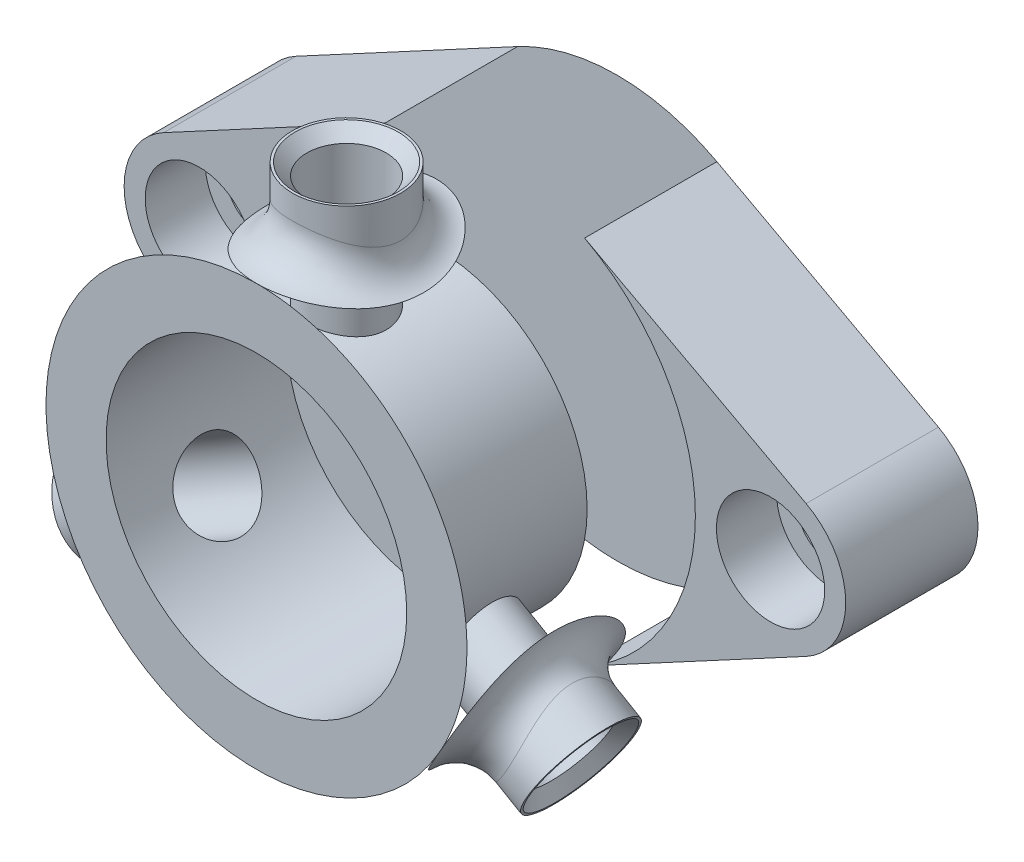
SolidWorks part; units mm, degrees
ref_plane "Front Plane" through (0, 0, 0) normal (0, 0, 1) x (1, 0, 0)
ref_plane "Top Plane" through (0, 0, 0) normal (0, 1, 0) x (1, 0, 0)
ref_plane "Right Plane" through (0, 0, 0) normal (1, 0, 0) x (0, 0, -1)
sketch "Sketch1" plane through (0, 0, 0) normal (0, 0, 1) x (1, 0, 0)
  circle A0 centre (0, 0) radius 12.5
  circle A1 centre (0, 0) radius 17.5
  dimension "D1" = 25
  dimension "D2" = 5
extrude "Boss-Extrude1" add sketch "Sketch1" along normal blind 15
sketch "Sketch2" plane through (0, 0, 0) normal (0, 0, -1) x (-1, 0, 0)
  circle A0 centre (0, 0) radius 17.5
  dimension "D1" = 35
extrude "Boss-Extrude2" add sketch "Sketch2" along normal blind 15
ref_plane "Plane1" through (0, 22.5, 0) normal (0, 1, 0) x (1, 0, 0)
sketch "Sketch3" plane through (0, 22.5, 0) normal (0, 1, 0) x (1, 0, 0)
  line L0 (-17.5, -15) -> (17.5, -15) construction
  circle A0 centre (0, -7.5) radius 4.5
  dimension "D1" = 9
  dimension "D2" = 7.5
extrude "Boss-Extrude3" add sketch "Sketch3" against normal up to surface (5 mm away) up to face at (17.5, 0, 15)
sketch "Sketch4" plane through (0, 22.5, 0) normal (0, 1, 0) x (1, 0, 0)
  circle A0 centre (0, -7.5) radius 3.3
  dimension "D1" = 6.6
extrude "Cut-Extrude1" cut sketch "Sketch4" against normal up to surface (10 mm away) up to face at (12.5, 0, 15)
pattern_circular "CirPattern1" count 3 over 360 about axis through (0, 0, 15) along (0, 0, 1) of "Boss-Extrude3", "Cut-Extrude1"
fillet "Fillet1" radius 3 3 edges at (12.458, -12.2901, 6.6272) (-16.8726, -4.6439, 6.6272) (-0.8714, 17.4783, 3.0852)
chamfer "Chamfer1" distance 1 angle 45 3 edges at (-19.4856, -11.25, 10.8) (19.4856, -11.25, 10.8) (0, 22.5, 10.8)
sketch "Sketch5" plane through (0, 0, -15) normal (0, 0, -1) x (-1, 0, 0)
  line L0 (26.7105, 5.5043) -> (8.2895, 15.4122)
  line L1 (26.7105, -5.5043) -> (8.2895, -15.4122)
  line L2 (-8.2895, 15.4122) -> (-26.7105, 5.5043)
  line L3 (-8.2895, -15.4122) -> (-26.7105, -5.5043)
  circle A0 centre (23.75, 0) radius 2.75
  circle A1 centre (-23.75, 0) radius 2.75
  arc A2 (26.7105, -5.5043) -> (26.7105, 5.5043) centre (23.75, 0) ccw
  arc A3 (-26.7105, 5.5043) -> (-26.7105, -5.5043) centre (-23.75, 0) ccw
  arc A4 (15.1554, -8.75) -> (0, 17.5) centre (0, 0) ccw construction
  arc A6 (-15.1554, -8.75) -> (15.1554, -8.75) centre (0, 0) ccw construction
  arc A8 (0, 17.5) -> (-15.1554, -8.75) centre (0, 0) ccw construction
  arc A9 (8.2895, 15.4122) -> (-8.2895, 15.4122) centre (0, 0) ccw
  arc A10 (8.2895, -15.4122) -> (-8.2895, -15.4122) centre (0, 0) cw
  dimension "D3" = 5.5
  dimension "D1" = 23.75
  dimension "D2" = 23.75
extrude "Boss-Extrude4" add sketch "Sketch5" against normal blind 11
sketch "Sketch6" plane through (0, 0, -4) normal (0, 0, 1) x (1, 0, 0)
  circle A0 centre (-23.75, 0) radius 4.5
  circle A1 centre (23.75, 0) radius 4.5
  dimension "D1" = 9
extrude "Cut-Extrude2" cut sketch "Sketch6" against normal blind 5
